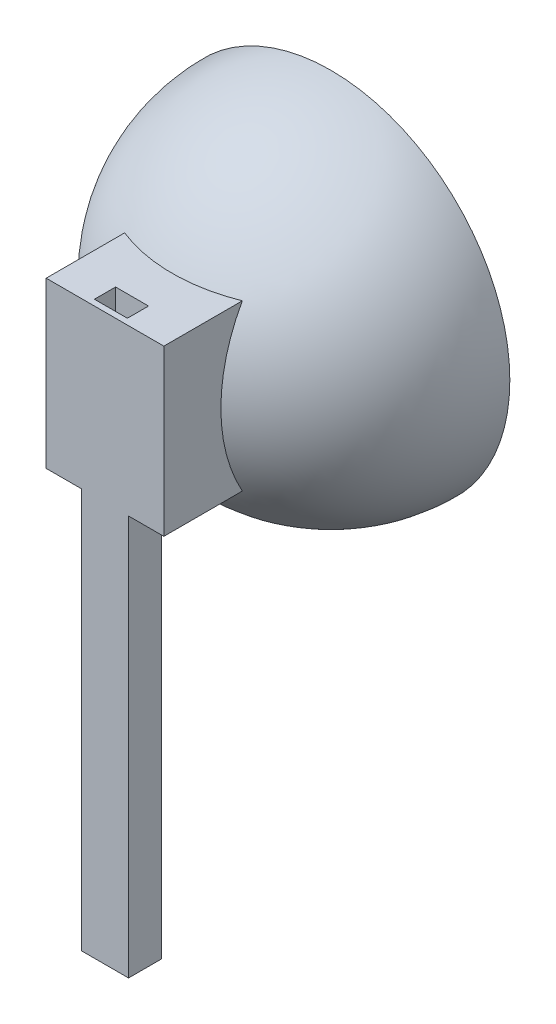
SolidWorks part; units mm, degrees
material "Commercially Pure CP-Ti UNS R50400 (SS)"
ref_plane "Front Plane" through (0, 0, 0) normal (0, 0, 1) x (1, 0, 0)
ref_plane "Top Plane" through (0, 0, 0) normal (0, 1, 0) x (1, 0, 0)
ref_plane "Right Plane" through (0, 0, 0) normal (1, 0, 0) x (0, 0, -1)
sketch "Sketch1" plane through (0, 0, 0) normal (0, 0, 1) x (1, 0, 0)
  line L0 (0, 33) -> (0, -33) construction
  line L1 (0, 38) -> (0, 33)
  line L2 (0, -33) -> (0, -38)
  arc A0 (0, -33) -> (0, 33) centre (0, 0) ccw
  arc A1 (0, -38) -> (0, 38) centre (0, 0) ccw
revolve "Revolve1" add sketch "Sketch1" angle 180 about L2
ref_plane "Plane1" through (0, 0, 38) normal (0, 0, -1) x (-1, 0, 0)
sketch "Sketch2" plane through (0, 0, 38) normal (0, 0, -1) x (-1, 0, 0)
  line L1 (-12.5, -17.5) -> (12.5, -17.5)
  line L2 (-12.5, -17.5) -> (-12.5, 17.5)
  line L3 (-12.5, 17.5) -> (12.5, 17.5)
  line L4 (12.5, -17.5) -> (12.5, 17.5)
  line L5 (-12.5, -17.5) -> (12.5, 17.5) construction
  line L6 (-12.5, 17.5) -> (12.5, -17.5) construction
  point P0 (0, 0)
  dimension "D1" = 35
  dimension "D2" = 25
extrude "Boss-Extrude2" add sketch "Sketch2" along normal up to body and the other way blind 10 separate body
sketch "Sketch5" plane through (0, 0, 48) normal (0, 0, 1) x (1, 0, 0)
  line L0 (-12.5, 17.5) -> (12.5, 17.5) construction
  line L4 (-5, 17.5) -> (5, 17.5)
  line L5 (0, -3.0387) -> (0, 116.9613) construction
  line L8 (-5, 17.5) -> (-5, -102.5)
  line L9 (-5, -102.5) -> (5, -102.5)
  line L10 (5, 17.5) -> (5, -102.5)
  dimension "D1" = 10
  dimension "D3" = 120
extrude "Boss-Extrude3" add sketch "Sketch5" against normal blind 7
sketch "Sketch6" plane through (0, -102.5, 0) normal (0, -1, 0) x (-1, 0, 0)
  line L0 (-5, -41) -> (-5, -48) construction
  line L1 (-3.5, -42.25) -> (3.5, -42.25)
  line L2 (-3.5, -42.25) -> (-3.5, -46.75)
  line L3 (-3.5, -46.75) -> (3.5, -46.75)
  line L4 (3.5, -42.25) -> (3.5, -46.75)
  line L5 (-5, -41) -> (5, -41) construction
  line L6 (5, -41) -> (5, -48) construction
  line L7 (5, -48) -> (-5, -48) construction
  dimension "D1" = 1.5
  dimension "D2" = 1.25
  dimension "D3" = 1.5
  dimension "D4" = 1.25
extrude "Cut-Extrude1" cut sketch "Sketch6" against normal blind 265
sketch "Sketch7" plane through (0, 0, 0) normal (1, 0, 0) x (0, 0, -1)
  point P5 (-44.5, 0)
sketch "Sketch8" plane through (0, 0, 0) normal (1, 0, 0) x (0, 0, -1)
  line L0 (-41, -102.5) -> (-48, -102.5) construction
  circle A0 centre (-44.5, -110) radius 7.5
  dimension "D1" = 15
